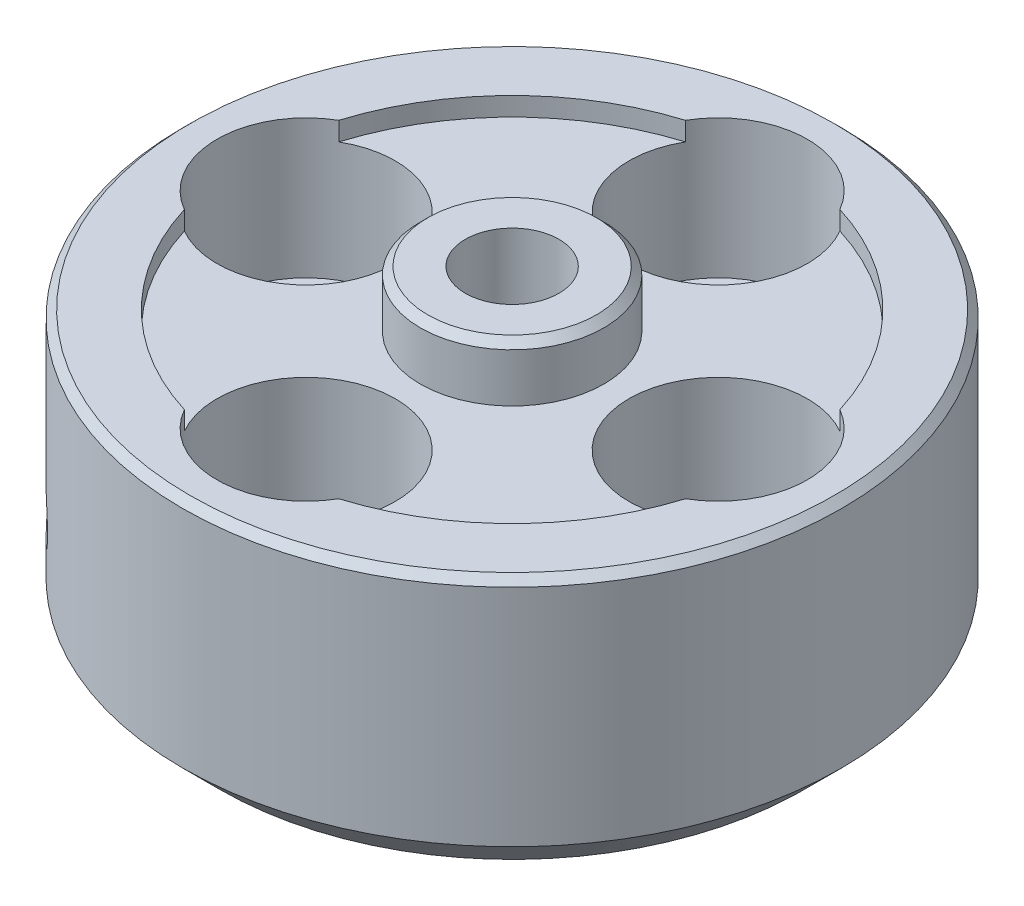
SolidWorks part; units mm, degrees
ref_plane "Front Plane" through (0, 0, 0) normal (0, 0, 1) x (1, 0, 0)
ref_plane "Top Plane" through (0, 0, 0) normal (0, 1, 0) x (1, 0, 0)
ref_plane "Right Plane" through (0, 0, 0) normal (1, 0, 0) x (0, 0, -1)
sketch "Sketch2" plane through (0, 0, 0) normal (0, 1, 0) x (1, 0, 0)
  circle A0 centre (0, 0) radius 11.176
  dimension "D1" = 22.352
extrude "Boss-Extrude1" add sketch "Sketch2" along normal blind 9.144
sketch "Sketch3" plane through (0, 9.144, 0) normal (0, 1, 0) x (1, 0, 0)
  circle A0 centre (0, 0) radius 8.89
  circle A1 centre (0, 0) radius 3.1115
  dimension "D1" = 17.78
  dimension "D2" = 6.223
extrude "Cut-Extrude1" cut sketch "Sketch3" against normal blind 0.635
sketch "Sketch4" plane through (0, 0, 0) normal (0, -1, 0) x (-1, 0, 0)
  circle A0 centre (0, 0) radius 3.0226
  dimension "D1" = 6.0452
extrude "Cut-Extrude2" cut sketch "Sketch4" against normal blind 5.334
sketch "Sketch6" plane through (0, 9.144, 0) normal (0, 1, 0) x (1, 0, 0)
  circle A0 centre (0, 6.985) radius 3.0226
  dimension "D2" = 6.0452
  dimension "D1" = 6.985
extrude "Cut-Extrude4" cut sketch "Sketch6" against normal blind 4.699
pattern_circular "CirPattern5" count 4 over 360 about axis through (0, 5.334, 0) along (0, -1, 0) of "Cut-Extrude4"
sketch "Sketch7" plane through (0, 9.144, 0) normal (0, 1, 0) x (1, 0, 0)
  circle A0 centre (0, 0) radius 1.5875
  dimension "D1" = 3.175
extrude "Cut-Extrude5" cut sketch "Sketch7" against normal blind 8.255
chamfer "Chamfer1" distance 0.254 angle 45 1 edges at (0, 9.144, 11.176)
chamfer "Chamfer2" distance 1.27 angle 45 1 edges at (0, 0, 11.176)
sketch "Sketch8" plane through (0, 4.445, 0) normal (0, 1, 0) x (1, 0, 0)
  circle A0 centre (0, 6.985) radius 0.9922
  dimension "D1" = 1.9844
extrude "Cut-Extrude6" cut sketch "Sketch8" against normal up to next
pattern_circular "CirPattern6" count 4 over 360 about axis through (0, 9.144, 0) along (0, -1, 0) of "Cut-Extrude6"
sketch "Sketch10" plane through (0, 9.144, 0) normal (0, 1, 0) x (1, 0, 0)
  circle A0 centre (0, 0) radius 1.5875
  circle A1 centre (0, 0) radius 3.1115
  dimension "D1" = 3.175
  dimension "D2" = 6.223
extrude "Boss-Extrude2" add sketch "Sketch10" along normal blind 1.27
chamfer "Chamfer3" distance 0.254 angle 45 1 edges at (0, 10.414, 3.1115)
ref_axis "Axis1" through (0, 8.2677, 0) along (0, -1, 0)
ref_plane "Plane1" through (0, 0, 0) normal (-0.7071, 0, 0.7071) x (0, -1, 0)
ref_plane "Plane2" through (-8.0822, 0, 8.0822) normal (-0.7071, 0, 0.7071) x (0, -1, 0)
sketch "Sketch12" plane through (-8.0822, 0, 8.0822) normal (-0.7071, 0, 0.7071) x (0, -1, 0)
  line L0 (-8.2677, 0) -> (0.3937, 0) construction
  line L1 (-1.27, 11.176) -> (-1.27, -11.176) construction
  circle A0 centre (-3.175, 0) radius 1.0922
  point P0 (-3.175, 0)
  dimension "D1" = 2.1844
  dimension "D2" = 1.905
hole_wizard "#2-56 Tapped Hole3" positions "Sketch12" profile "Sketch18" tap size "#2-56" standard "ANSI Inch"
sketch "Sketch18" plane through (-8.0822, 3.175, 8.0822) normal (0, 1, 0) x (0.7071, 0, 0.7071)
  line L0 (0, 0) -> (0, 11.9642)
  line L1 (0, 11.9642) -> (0.889, 11.43)
  line L2 (0.889, 11.43) -> (0.889, 0)
  line L5 (0.889, 0) -> (0, 0)
  line L10 (0, 11.9642) -> (-0.889, 11.43) construction
  line L11 (0, -6.35) -> (0, 107.95) construction
  dimension "Tap Drill Dia." = 1.778
  dimension "Tap Drill Depth" = 11.43
  dimension "Drill Angle" = 118
cosmetic thread "Hole Thread2" parameters "D1"=10.16, "D2"=2.1844
